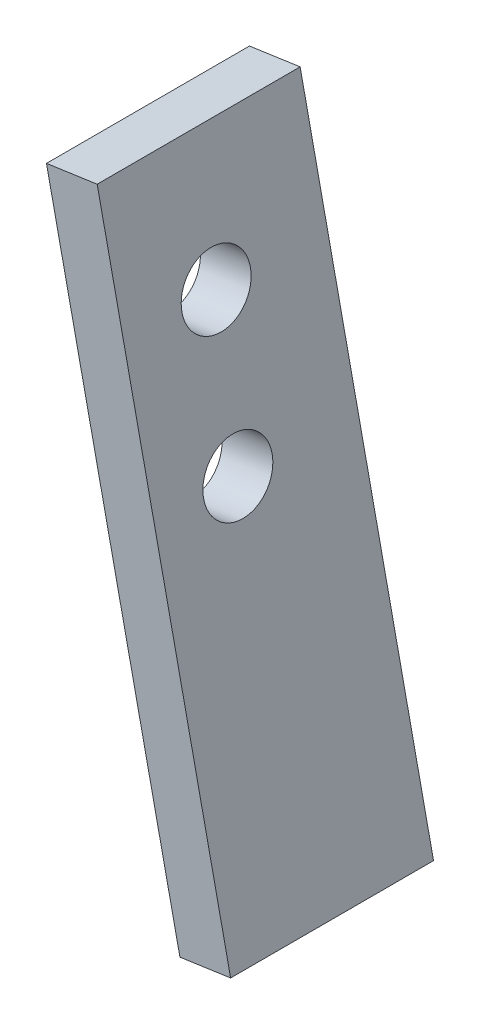
SolidWorks part; units mm, degrees
ref_plane "Front" through (0, 0, 0) normal (0, 0, 1) x (1, 0, 0)
ref_plane "Top" through (0, 0, 0) normal (0, 1, 0) x (1, 0, 0)
ref_plane "Right" through (0, 0, 0) normal (1, 0, 0) x (0, 0, -1)
ref_axis "Axis1" through (38.6204, -344.4414, 4.2776) along (-1, 0, 0)
ref_axis "Axis2" through (40.331, -22.98, 75.0619) along (-0.9898, -0.1426, 0)
ref_axis "Axis3" through (38.1486, -8.1395, 75.0619) along (-0.9898, -0.1426, 0)
ref_point "Point1"
ref_plane "Plane3" through (-15.2153, -2.5724, 84.9119) normal (-0.9898, -0.1426, 0) x (0, 0, 1)
sketch "Sketch2" plane through (-15.2153, -2.5724, 84.9119) normal (-0.9898, -0.1426, 0) x (0, 0, 1)
  line L0 (0, 0) -> (-19.8107, 0.0127)
  line L1 (-19.8107, 0.0127) -> (-23.557, -64.9849)
  line L2 (-23.557, -64.9849) -> (-3.7522, -64.9976)
  line L3 (-19.8107, 0.0127) -> (0, 0) construction
  line L4 (-19.8107, 0.0127) -> (-24.3108, -78.0635) construction
  line L5 (-4.5039, -78.0202) -> (0, 0) construction
  line L6 (-9.7572, -12.9983) -> (-9.7572, -27.8571) construction
  line L7 (-3.7522, -64.9976) -> (0, 0)
  circle A2 centre (-9.7572, -12.9983) radius 3.3779 construction
  circle A3 centre (-9.7572, -27.8571) radius 3.3779 construction
  circle A4 centre (-9.7572, -12.9983) radius 3.3779
  circle A5 centre (-9.7572, -27.8571) radius 3.3779
  point P11 (-3.8079, -65.9625)
  point P13 (-3.7522, -64.9976)
  dimension "D1" = 65
extrude "Boss-Extrude1" add sketch "Sketch2" against normal blind 5
